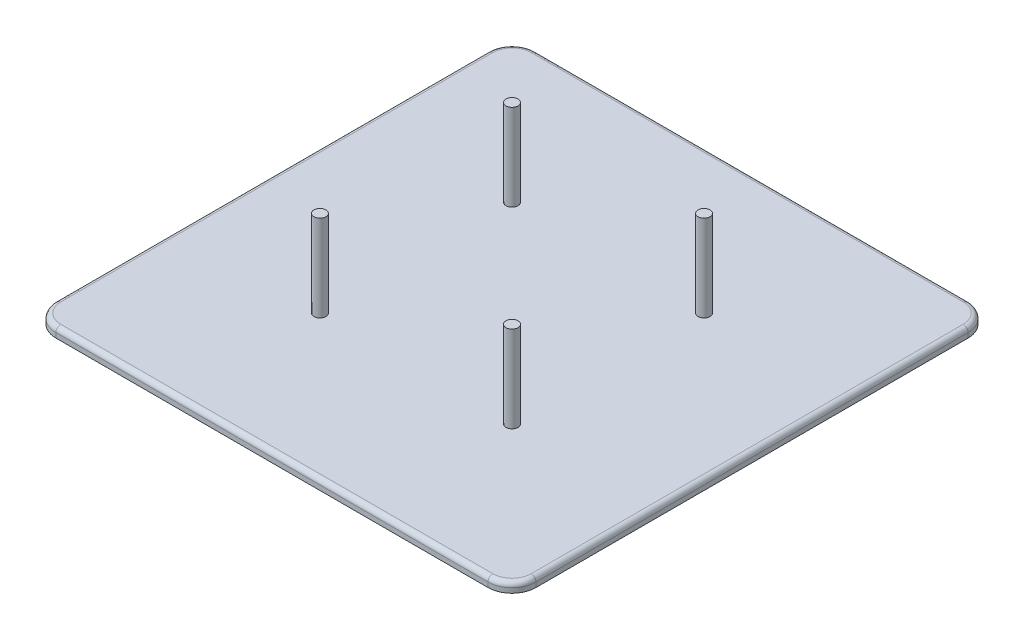
SolidWorks part; units mm, degrees
ref_plane "Front Plane" through (0, 0, 0) normal (0, 0, 1) x (1, 0, 0)
ref_plane "Top Plane" through (0, 0, 0) normal (0, 1, 0) x (1, 0, 0)
ref_plane "Right Plane" through (0, 0, 0) normal (1, 0, 0) x (0, 0, -1)
sketch "Sketch1" plane through (0, 0, 0) normal (0, 1, 0) x (1, 0, 0)
  line L0 (0, 50) -> (0, -50) construction
  line L1 (-50, 50) -> (50, 50)
  line L2 (-50, 50) -> (-50, -50)
  line L3 (-50, -50) -> (50, -50)
  line L4 (50, 50) -> (50, -50)
  line L5 (-50, 0) -> (50, 0) construction
  point P0 (0, 0)
  point P10 (0, 0)
  dimension "D1" = 100
  dimension "D2" = 100
extrude "Boss-Extrude1" add sketch "Sketch1" along normal blind 2
sketch "Sketch2" plane through (0, 0, 0) normal (0, 1, 0) x (1, 0, 0)
  circle A0 centre (-20, -20) radius 1.25
  circle A1 centre (-20, 20) radius 1.25
  circle A2 centre (20, 20) radius 1.25
  circle A3 centre (20, -20) radius 1.25
  point P14 (0, 0)
  point P23 (0, 0)
  dimension "D1" = 4
  dimension "D2" = 28.2843
extrude "Boss-Extrude2" add sketch "Sketch2" along normal blind 20
fillet "Fillet1" radius 1 4 edges at (50, 2, 0) (0, 2, -50) (-50, 2, 0) (0, 2, 50)
fillet "Fillet2" radius 5 8 edges at (-49.7071, 1.7071, 49.7071) (49.7071, 1.7071, 49.7071) (49.7071, 1.7071, -49.7071) (-49.7071, 1.7071, -49.7071) (-50, 0.5, -50) (50, 0.5, -50) (50, 0.5, 50) (-50, 0.5, 50)
